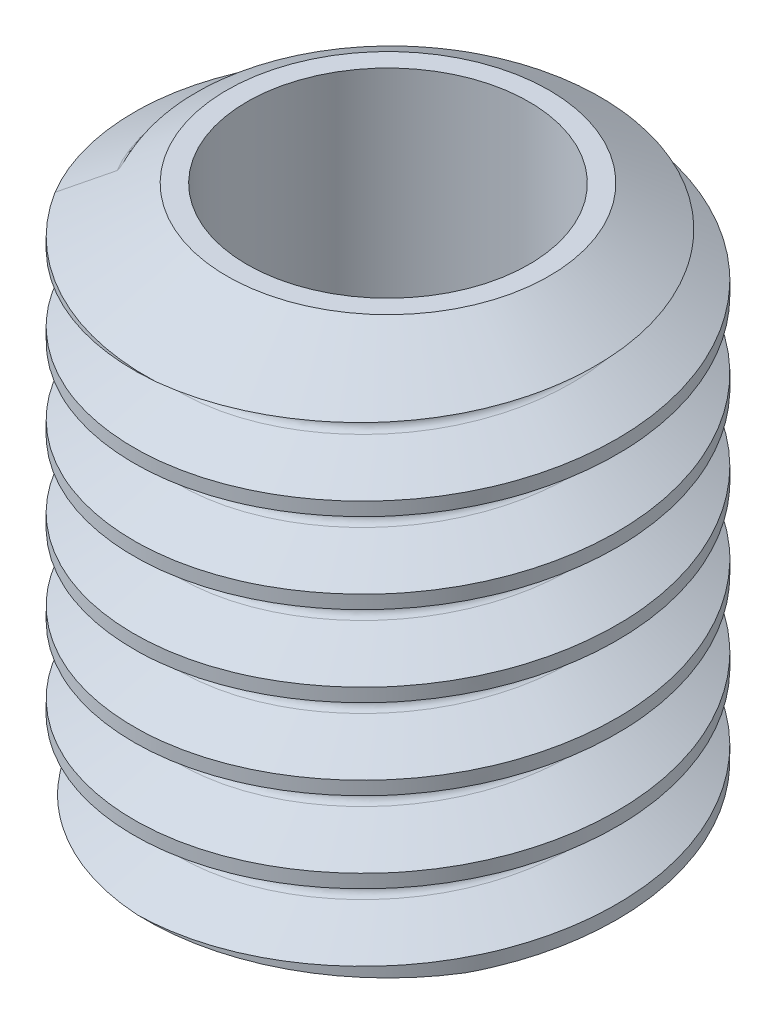
SolidWorks part; units mm, degrees
ref_plane "Front Plane" through (0, 0, 0) normal (0, 0, 1) x (1, 0, 0)
ref_plane "Top Plane" through (0, 0, 0) normal (0, 1, 0) x (1, 0, 0)
ref_plane "Right Plane" through (0, 0, 0) normal (1, 0, 0) x (0, 0, -1)
sketch "Sketch1" plane through (0, 0, 0) normal (0, 1, 0) x (1, 0, 0)
  circle A0 centre (0, 0) radius 3
  dimension "D1" = 6
extrude "Boss-Extrude1" add sketch "Sketch1" along normal blind 7
ref_plane "Plane1" through (0, 8, 0) normal (0, 1, 0) x (1, 0, 0)
sketch "Sketch2" plane through (0, 8, 0) normal (0, 1, 0) x (1, 0, 0)
  circle A0 centre (0, 0) radius 2.675
  dimension "D1" = 5.35
curve "Helix/Spiral1" pitch 1 height 9 radius 2.675 centre (0, 8, 0) axis (0, -1, 0) start towards (0, 0, 1)
sketch "Sketch3" plane through (0, 0, 0) normal (1, 0, 0) x (0, 0, -1)
  line L0 (0, 0) -> (0, 8) construction
  line L1 (0, 8) -> (-2.3865, 8) construction
  line L2 (0, 8) -> (0, 9) construction
  line L3 (0, 9) -> (-3, 9) construction
  line L4 (-3, 9) -> (-3, 7.5) construction
  line L5 (-2.3865, 8) -> (-3.3865, 8) construction
  line L6 (-2.3865, 8.0625) -> (-2.3865, 7.9375) construction
  line L7 (-2.3865, 8.0625) -> (-3.2525, 8.5625) construction
  line L8 (-2.3865, 7.9375) -> (-3.2525, 7.4375) construction
  line L9 (-2.4406, 8.0937) -> (-3, 8.4167)
  line L10 (-3, 8.4167) -> (-3, 7.5833)
  line L11 (-3, 7.5833) -> (-2.4406, 7.9063)
  arc A0 (-2.4406, 7.9063) -> (-2.4406, 8.0937) centre (-2.4948, 8) ccw
  point P10 (-3, 8.4167)
  point P15 (-3, 7.5833)
  dimension "D1" = 8
  dimension "D2" = 2.3865
  dimension "D3" = 3
  dimension "D4" = 1.5
  dimension "D5" = 1
  dimension "D6" = 1
  dimension "D7" = 0.0625
  dimension "D8" = 0.125
  dimension "D9" = 1
  dimension "D10" = 1
  dimension "D11" = 30
  dimension "D12" = 60
sweep "Cut-Sweep1" cut profiles "Sketch3" path "Helix/Spiral1" align with end faces yes
sketch "Sketch4" plane through (0, 0, 0) normal (1, 0, 0) x (0, 0, -1)
  line L0 (3, 0) -> (0, 0) construction
  line L1 (-2.0345, 0) -> (2.6029, 0) construction
  line L2 (0, 0) -> (0, 7) construction
  line L3 (2.6029, 7) -> (-2.0345, 7) construction
  line L4 (0, 7) -> (3, 7) construction
  line L5 (3, 7) -> (2, 7)
  line L6 (2, 7) -> (3, 6.4226)
  line L7 (3, 6.4226) -> (3, 7)
  line L8 (3, 0) -> (2, 0)
  line L11 (3, 0) -> (3, 0.5774)
  line L12 (3, 0.5774) -> (2, 0)
  dimension "D1" = 3
  dimension "D2" = 3
  dimension "D3" = 1
  dimension "D4" = 60
  dimension "D5" = 1
  dimension "D6" = 30
sketch "Sketch5" plane through (0, 0, 0) normal (0, 1, 0) x (1, 0, 0)
  circle A0 centre (0, 0) radius 1.75
  dimension "D1" = 3.5
extrude "Cut-Extrude2" cut sketch "Sketch5" along normal through all
revolve "Cut-Revolve2" cut sketch "Sketch4" angle 360 about L2
